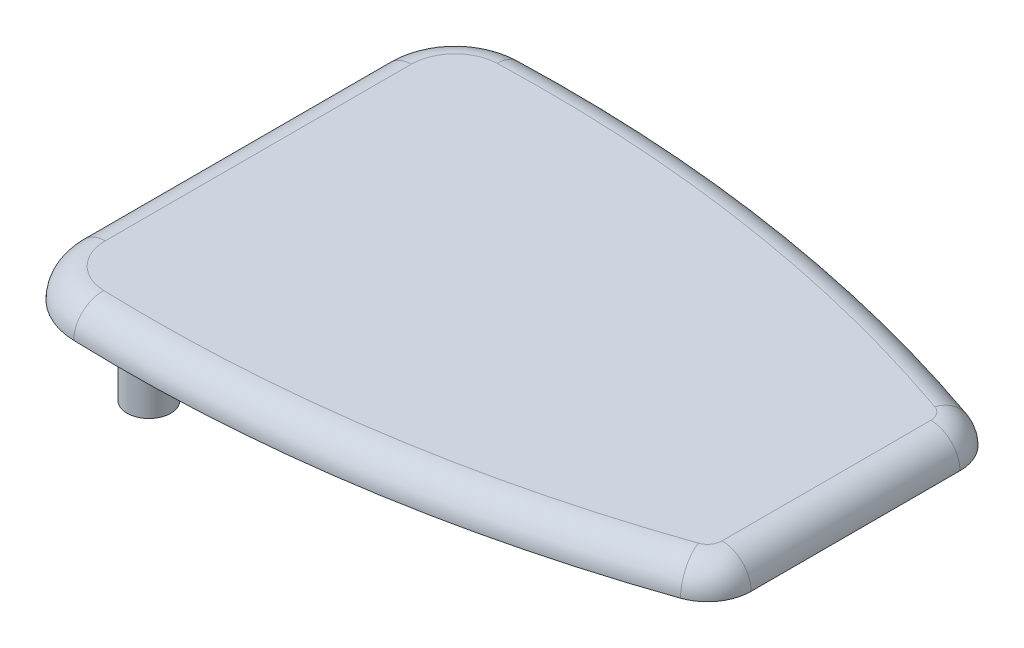
SolidWorks part; units mm, degrees
ref_plane "Front Plane" through (0, 0, 0) normal (0, 0, 1) x (1, 0, 0)
ref_plane "Top Plane" through (0, 0, 0) normal (0, 1, 0) x (1, 0, 0)
ref_plane "Right Plane" through (0, 0, 0) normal (1, 0, 0) x (0, 0, -1)
sketch "Sketch1" plane through (0, 0, 0) normal (0, 1, 0) x (1, 0, 0)
  line L0 (0, 0) -> (-43, 0) construction
  line L1 (0, -7.1666) -> (0, 7.1666)
  line L4 (-43, 10.5027) -> (-43, -10.5027)
  arc A0 (0, 7.1666) -> (-2.0141, 10) centre (-3, 7.1666) ccw
  arc A1 (0, -7.1666) -> (-2.0141, -10) centre (-3, -7.1666) cw
  arc A2 (-38.1644, 15.5) -> (-43, 10.5027) centre (-38, 10.5027) ccw
  arc A3 (-38.1644, -15.5) -> (-43, -10.5027) centre (-38, -10.5027) cw
  arc A4 (-2.0141, 10) -> (-38.1644, 15.5) centre (-34.8769, -84.4459) ccw
  arc A5 (-2.0141, -10) -> (-38.1644, -15.5) centre (-34.8769, 84.4459) cw
  point P17 (-31.9353, 15.5)
  point P18 (0, 0)
  point P19 (-39.488, 15.5)
  point P20 (-2.1837, 10)
  point P21 (-2.1837, -10)
  point P22 (-2.1837, 10)
  point P23 (-2.0861, 11.3718)
  point P24 (-29.1236, 18.6719)
  point P25 (-43, 11.5447)
  dimension "D1" = 100
  dimension "D2" = 3
  dimension "D3" = 5
  dimension "D6" = 20
  dimension "D4" = 43
  dimension "D5" = 31
extrude "Boss-Extrude1" add sketch "Sketch1" along normal mid plane 2
sketch "Sketch2" plane through (0, -1, 0) normal (0, -1, 0) x (1, 0, 0)
  line L0 (0, 7.1666) -> (0, -7.1666) construction
  circle A0 centre (-8, 0) radius 2.5
  circle A3 centre (-8, 0) radius 1.5
  dimension "D1" = 8
  dimension "D2" = 5
  dimension "D3" = 3
extrude "Boss-Extrude2" add sketch "Sketch2" along normal blind 1
extrude "Boss-Extrude3" add sketch "Sketch2<2>" along normal blind 6 contours A3 region at (-8, -1, 0)
sketch "Sketch2<2>" plane through (0, -1, 0) normal (0, -1, 0) x (1, 0, 0) same geometry as "Sketch2"
sketch "Sketch3" plane through (0, -1, 0) normal (0, -1, 0) x (1, 0, 0)
  point P0 (-38, 10.5027)
  point P1 (-38, -10.5027)
pattern_sketch "Sketch-Pattern1" of "Boss-Extrude2", "Boss-Extrude3" driven by "Sketch3"
fillet "Fillet1" radius 2 8 edges at (-19.8357, 1, 14.4164) (-41.5932, 1, 13.9796) (-43, 1, 0) (-41.5932, 1, -13.9796) (-0.5548, 1, -8.9048) (0, 1, 0) (-0.5548, 1, 8.9048) (-19.8357, 1, -14.4164)
